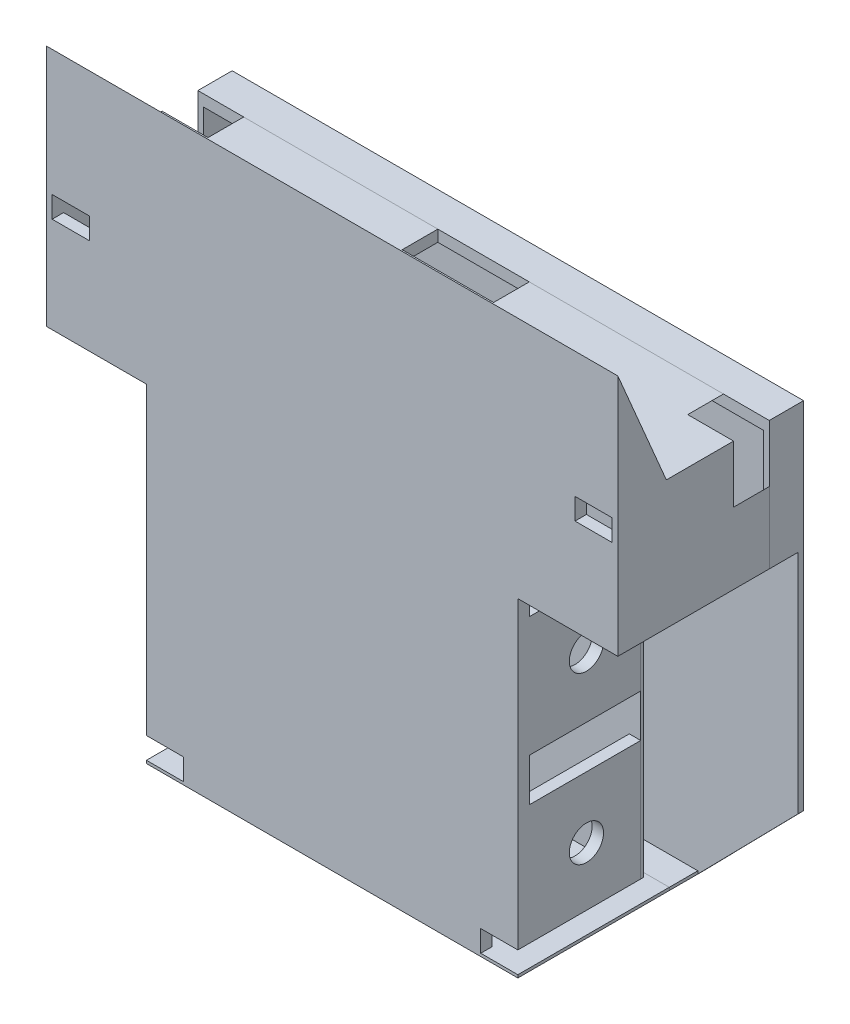
SolidWorks part; units mm, degrees
material "Malleable Cast Iron"
ref_plane "Alzado" through (0, 0, 0) normal (0, 0, 1) x (1, 0, 0)
ref_plane "Planta" through (0, 0, 0) normal (0, 1, 0) x (1, 0, 0)
ref_plane "Vista lateral" through (0, 0, 0) normal (1, 0, 0) x (0, 0, -1)
sketch "Sketch1" plane through (0, 0, 0) normal (0, 0, 1) x (1, 0, 0)
  line L0 (0, 160) -> (200, 160)
  line L5 (0, 0) -> (200, 0)
  line L6 (0, 0) -> (0, 200)
  line L7 (0, 200) -> (200, 200)
  line L8 (200, 0) -> (200, 200)
  line L9 (0, 0) -> (35, 0)
  line L10 (0, 0) -> (0, 55)
  line L11 (0, 55) -> (35, 55)
  line L12 (35, 0) -> (35, 55)
  line L13 (200, 0) -> (165, 0)
  line L14 (200, 0) -> (200, 55)
  line L15 (200, 55) -> (165, 55)
  line L16 (165, 0) -> (165, 55)
  line L17 (0, 135.9584) -> (24.0416, 160)
  line L19 (175.9584, 160) -> (200, 135.9584)
  line L20 (35, 55) -> (35, 60)
  line L21 (0, 115) -> (35, 115)
  line L22 (0, 115) -> (0, 60)
  line L23 (0, 60) -> (35, 60)
  line L24 (35, 115) -> (35, 60)
  line L25 (200, 115) -> (165, 115)
  line L26 (200, 115) -> (200, 60)
  line L27 (200, 60) -> (165, 60)
  line L28 (165, 115) -> (165, 60)
  line L29 (165, 60) -> (165, 55)
  dimension "D1" = 200
  dimension "D2" = 200
  dimension "D3" = 55
  dimension "D4" = 55
  dimension "D5" = 35
  dimension "D6" = 35
  dimension "D7" = 40
  dimension "D8" = 45
  dimension "D9" = 34
  dimension "D10" = 45
  dimension "D11" = 55
  dimension "D12" = 35
  dimension "D13" = 5
  dimension "D14" = 5
extrude "Boss-Extrude1" add sketch "Sketch1" along normal blind 4 contours L28 L25 L8 L0 L6 L21 L24 L23 L11 L12 L5 L16 L15 L27 region at (100, 85.9694, 0)
sketch "Sketch3" plane through (0, 0, 4) normal (0, 0, 1) x (1, 0, 0)
  line L1 (0, 0) -> (200, 0)
  line L2 (0, 0) -> (0, 1)
  line L3 (0, 160) -> (200, 160)
  line L4 (200, 0) -> (200, 1)
  line L5 (200, 115) -> (198, 115)
  line L6 (2, 156) -> (198, 156)
  line L7 (2, 156) -> (2, 115)
  line L8 (1, 1) -> (199, 1)
  line L9 (198, 156) -> (198, 115)
  line L10 (199, 1) -> (200, 1)
  line L11 (1, 1) -> (0, 1)
  line L12 (0, 115) -> (2, 115)
  line L13 (0, 115) -> (0, 160)
  line L14 (200, 115) -> (200, 160)
  line L15 (200, 115) -> (200, 135.9584) construction
  line L16 (24.0416, 160) -> (175.9584, 160) construction
  dimension "D2" = 1
  dimension "D3" = 2
  dimension "D4" = 2
  dimension "D5" = 4
extrude "Boss-Extrude2" add sketch "Sketch3" against normal blind 53
sketch "Sketch4" plane through (200, 0, 0) normal (1, 0, 0) x (0, 0, -1)
  line L0 (-4, 160) -> (-4, 200)
  line L1 (-4, 200) -> (12.979, 160)
  line L3 (12.979, 160) -> (-4, 160)
  line L4 (49, 160) -> (-4, 160) construction
  line L5 (-4, 115) -> (-4, 160) construction
  dimension "D1" = 23
  dimension "D2" = 40
extrude "Boss-Extrude4" add sketch "Sketch4" against normal up to surface (200 mm away) up to face at (0, 0.5, -22.5)
ref_axis "Axis1" through (179.9584, 156, 0) along (0.7071, -0.7071, 0)
ref_axis "Axis2" through (2, 137.9584, 0) along (0.7071, 0.7071, 0)
ref_plane "Plane1" through (-67.9792, 67.9792, 0) normal (-0.7071, 0.7071, 0) x (0.7071, 0.7071, 0)
sketch "Sketch5" plane through (-67.9792, 67.9792, 0) normal (-0.7071, 0.7071, 0) x (0.7071, 0.7071, 0)
  line L1 (98.9655, 36.5) -> (124.4802, 36.5)
  line L2 (98.9655, 36.5) -> (98.9655, 49)
  line L3 (98.9655, 49) -> (124.4802, 49)
  line L4 (124.4802, 36.5) -> (124.4802, 49)
  line L8 (111.7229, 49) -> (82.7315, 49) construction
  dimension "D2" = 12.5
extrude "Cut-Extrude1" cut sketch "Sketch5" along normal blind 20
ref_plane "Plane2" through (167.9792, 167.9792, 0) normal (0.7071, 0.7071, 0) x (0, 0, -1)
sketch "Sketch6" plane through (167.9792, 167.9792, 0) normal (0.7071, 0.7071, 0) x (0, 0, -1)
  line L1 (36.5, -16.9411) -> (49, -16.9411)
  line L2 (36.5, -16.9411) -> (36.5, -42.4558)
  line L3 (36.5, -42.4558) -> (49, -42.4558)
  line L4 (49, -16.9411) -> (49, -42.4558)
  line L5 (49, -141.4214) -> (49, -140.7142) construction
  dimension "D2" = 12.5
extrude "Cut-Extrude2" cut sketch "Sketch6" along normal blind 20
sketch "Sketch8" plane through (0, 0, 4) normal (0, 0, 1) x (1, 0, 0)
  line L0 (20.0416, 156) -> (2, 156)
  line L1 (2, 156) -> (2, 137.9584)
  line L2 (2, 137.9584) -> (20.0416, 156)
  line L3 (179.9584, 156) -> (198, 156)
  line L4 (198, 156) -> (198, 137.9584)
  line L5 (198, 137.9584) -> (179.9584, 156)
extrude "Boss-Extrude5" add sketch "Sketch8" against normal blind 4
sketch "Sketch9" plane through (0, 0, 0) normal (0, 0, -1) x (-1, 0, 0)
  line L0 (-35, 1) -> (-165, 1) construction
  line L1 (-35.5503, 107.5) -> (-39.5503, 107.5)
  line L2 (-35.5503, 107.5) -> (-35.5503, 8.5)
  line L3 (-35.5503, 8.5) -> (-39.5503, 8.5)
  line L4 (-39.5503, 107.5) -> (-39.5503, 8.5)
  line L6 (-165, 107.5) -> (-161, 107.5)
  line L7 (-165, 107.5) -> (-165, 8.5)
  line L8 (-165, 8.5) -> (-161, 8.5)
  line L9 (-161, 107.5) -> (-161, 8.5)
  line L10 (-198, 115) -> (-165, 115) construction
  line L11 (-2, 115) -> (-35, 115) construction
  point P14 (-163, 8.5)
  dimension "D1" = 4
  dimension "D2" = 4
  dimension "D3" = 7.5
  dimension "D4" = 7.5
  dimension "D5" = 7.5
  dimension "D6" = 7.5
extrude "Boss-Extrude6" add sketch "Sketch9" along normal blind 39
sketch "Sketch10" plane through (165, 0, 0) normal (1, 0, 0) x (0, 0, -1)
  line L0 (39, 107.5) -> (39, 8.5) construction
  line L1 (39, 65.5) -> (0, 65.5)
  line L2 (39, 65.5) -> (39, 50.5)
  line L3 (39, 50.5) -> (0, 50.5)
  line L4 (0, 65.5) -> (0, 50.5)
  line L8 (0, 8.5) -> (0, 107.5) construction
  line L9 (39, 8.5) -> (0, 8.5) construction
  dimension "D1" = 15
  dimension "D2" = 42
extrude "Cut-Extrude5" cut sketch "Sketch10" against normal blind 137
sketch "Sketch12" plane through (0, 1, 0) normal (0, 1, 0) x (1, 0, 0)
  line L1 (35, -4) -> (0, -4)
  line L2 (35, -4) -> (35, 49)
  line L3 (35, 49) -> (0, 49)
  line L4 (0, -4) -> (0, 49)
  line L5 (165, -4) -> (200, -4)
  line L6 (165, -4) -> (165, 49)
  line L7 (165, 49) -> (200, 49)
  line L8 (200, -4) -> (200, 49)
extrude "Cut-Extrude6" cut sketch "Sketch12" against normal blind 8
sketch "Sketch13" plane through (165, 0, 0) normal (1, 0, 0) x (0, 0, -1)
  line L0 (-4, 115) -> (-4, 0) construction
  line L1 (39, 107.5) -> (0, 107.5) construction
  line L2 (39, 8.5) -> (0, 8.5) construction
  circle A0 centre (20, 87) radius 6
  circle A1 centre (20, 29) radius 6
  dimension "D1" = 12
  dimension "D2" = 24
  dimension "D3" = 20.5
  dimension "D4" = 24
  dimension "D5" = 20.5
extrude "Cut-Extrude7" cut sketch "Sketch13" against normal blind 135
sketch "Sketch15" plane through (0, 0, -39) normal (0, 0, -1) x (-1, 0, 0)
  line L1 (-165, 107.5) -> (-35.5503, 107.5)
  line L2 (-165, 107.5) -> (-165, 8.5)
  line L3 (-165, 8.5) -> (-35.5503, 8.5)
  line L4 (-35.5503, 107.5) -> (-35.5503, 8.5)
extrude "Boss-Extrude7" add sketch "Sketch15" along normal blind 1
sketch "Sketch16" plane through (165, 0, 0) normal (1, 0, 0) x (0, 0, -1)
  line L0 (39, 107.5) -> (39, 8.5)
  line L1 (40, 107.5) -> (0, 107.5) construction
  line L2 (40, 8.5) -> (0, 8.5) construction
  line L3 (39, 65.5) -> (39, 50.5) construction
split "Split1" trim tools "Sketch16" bodies to split 140 resulting bodies 141 142
sketch "Sketch17" plane through (0, 0, 0) normal (0, 0, -1) x (-1, 0, 0)
  line L0 (-179.9584, 156) -> (-198, 156) construction
  line L1 (-198, 156) -> (-185, 156)
  line L2 (-198, 156) -> (-198, 148.5)
  line L3 (-198, 148.5) -> (-185, 148.5)
  line L4 (-185, 156) -> (-185, 148.5)
  line L5 (-198, 156) -> (-198, 137.9584) construction
  line L7 (-2, 156) -> (-15, 156)
  line L8 (-2, 156) -> (-2, 148.5)
  line L9 (-2, 148.5) -> (-15, 148.5)
  line L10 (-15, 156) -> (-15, 148.5)
  line L11 (-165, 1) -> (-152, 1)
  line L12 (-165, 1) -> (-165, 8.5)
  line L13 (-165, 8.5) -> (-152, 8.5)
  line L14 (-152, 1) -> (-152, 8.5)
  line L15 (-35, 1) -> (-48, 1)
  line L16 (-35, 1) -> (-35, 8.5)
  line L17 (-35, 8.5) -> (-48, 8.5)
  line L18 (-48, 1) -> (-48, 8.5)
  dimension "D1" = 13
  dimension "D2" = 7.5
extrude "Cut-Extrude8" cut sketch "Sketch17" against normal blind 10
sketch "Sketch21" plane through (0, 0, -49) normal (0, 0, -1) x (-1, 0, 0)
  line L0 (-200, 115) -> (-200, 139.9584) construction
  line L1 (0, 115) -> (-2, 115)
  line L2 (0, 115) -> (0, 160)
  line L3 (0, 160) -> (-200, 160)
  line L4 (-200, 115) -> (-200, 160)
  line L5 (0, 160) -> (-200, 160) construction
  line L6 (-2, 115) -> (-2, 156)
  line L7 (-2, 156) -> (-198, 156)
  line L8 (-198, 156) -> (-198, 115)
  line L9 (-198, 115) -> (-198, 156)
  line L10 (-20.0416, 156) -> (-179.9584, 156) construction
  line L11 (-198, 115) -> (-200, 115)
  line L13 (-35, 0) -> (-165, 0)
  line L14 (-35, 0) -> (-35, 1)
  line L15 (-35, 1) -> (-165, 1)
  line L16 (-165, 0) -> (-165, 1)
  line M8 (0, 115) -> (0, 139.9584)
  line M9 (0, 139.9584) -> (-2, 137.9584)
  line M10 (-2, 137.9584) -> (-2, 115)
  line M11 (-2, 115) -> (0, 115)
extrude "Boss-Extrude10" add sketch "Sketch21" along normal blind 10 contours M11 M8 M9 M10 | L11 L8 L7 L6 L2 L3 L4 M9 | L15 L16 L13 L14 region at (0.9861, 126.9861, -49) region at (1.145, 139.1033, -49)
sketch "Sketch22" plane through (0, 0, -59) normal (0, 0, -1) x (-1, 0, 0)
  line L0 (-200, 115) -> (-200, 160) construction
  line L1 (0, 160) -> (-200, 160)
  line L2 (0, 160) -> (0, 0)
  line L3 (0, 0) -> (-200, 0)
  line L4 (-200, 160) -> (-200, 0)
  line L5 (-35, 0) -> (-165, 0) construction
  line L6 (-35, 0) -> (0, 35.7071)
  line L7 (-165, 0) -> (-200, 35.7071)
  point P12 (-200, 70)
  point P17 (0, 70)
  line M7 (-2, 115) -> (0, 115)
  line M8 (0, 115) -> (0, 160)
  line M9 (0, 160) -> (-200, 160)
  line M10 (-200, 160) -> (-200, 115)
  line M11 (-200, 115) -> (-198, 115)
  line M12 (-198, 115) -> (-198, 156)
  line M13 (-198, 156) -> (-2, 156)
  line M14 (-2, 156) -> (-2, 115)
  dimension "D1" = 90
  dimension "D2" = 50
sketch "Sketch23" plane through (0, 160, 0) normal (0, 1, 0) x (1, 0, 0)
  line L0 (0, 49) -> (16.0416, 49) construction
  line L1 (84, 36.5) -> (116, 36.5)
  line L2 (84, 36.5) -> (84, 49)
  line L3 (84, 49) -> (116, 49)
  line L4 (116, 36.5) -> (116, 49)
  line L5 (84, 36.5) -> (116, 49) construction
  line L6 (84, 49) -> (116, 36.5) construction
  line L7 (16.0416, 36.5) -> (0, 36.5) construction
  line L8 (200, 36.5) -> (200, 12.979) construction
  point P0 (100, 42.75)
  dimension "D1" = 100
  dimension "D2" = 32
extrude "Cut-Extrude9" cut sketch "Sketch23" against normal blind 10
extrude "Boss-Extrude14" add sketch "Sketch22" along normal blind 2 contours L7 L3 L6 L2 L4 M7 M14 M13 M12 M11 | M14 M7 M8 M9 M10 M11 M12 M13 region at (0.205, 137.5, -59) region at (100, 80.4567, -59)
sketch "Sketch24" plane through (0, 160, 0) normal (0, 1, 0) x (1, 0, 0)
  line L0 (0, 49) -> (200, 49)
split "Split2" trim tools "Sketch24" bodies to split 149 resulting bodies 150 151
